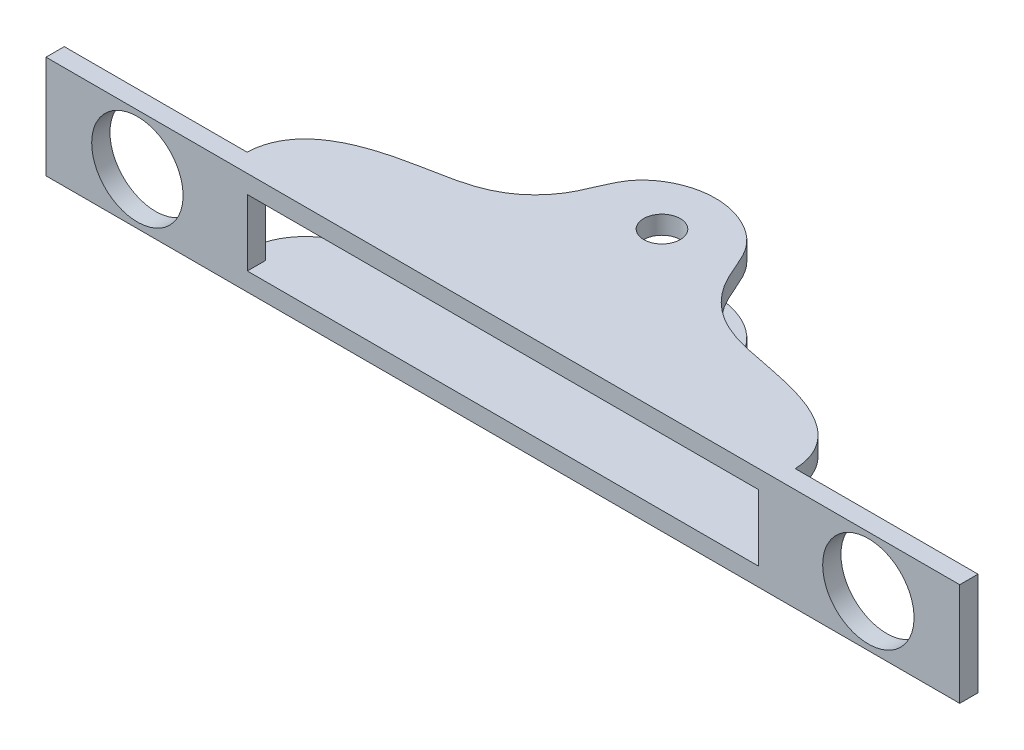
SolidWorks part; units mm, degrees
material "6061 Alloy"
ref_plane "Front Plane" through (0, 0, 0) normal (0, 0, 1) x (1, 0, 0)
ref_plane "Top Plane" through (0, 0, 0) normal (0, 1, 0) x (1, 0, 0)
ref_plane "Right Plane" through (0, 0, 0) normal (1, 0, 0) x (0, 0, -1)
sketch "Sketch2" plane through (0, 0, 0) normal (0, 1, 0) x (1, 0, 0)
  line L0 (0, 0) -> (25.4, 0) construction
  line L1 (0, 0) -> (-25.4, 0) construction
  line L2 (0, 24.8691) -> (0, -5.2934) construction
  line L3 (0, -5.2934) -> (0, 0) construction
  line L4 (0, 9.7878) -> (0, 24.8691) construction
  line L5 (-25.4, 0) -> (-31.75, 0)
  line L6 (25.4, 0) -> (31.75, 0)
  line L7 (-25.4, 0) -> (-19.05, 0)
  line L8 (19.05, 0) -> (25.4, 0)
  line L9 (-31.75, 0) -> (-31.75, -1.27)
  line L10 (-31.75, -1.27) -> (31.75, -1.27)
  line L11 (31.75, -1.27) -> (31.75, 0)
  line L12 (-19.05, 0) -> (19.05, 0)
  circle A0 centre (0, 9.7878) radius 1.27
  spline S0 degree 3 poles (19.05, 0) (18.925, 3.1125) (13.8714, 5.1827) (8.1004, 5.6407) (5.1505, 8.7108) (4.2338, 12.3346) (1.4648, 13.5252) (0, 13.4975) knots 0 0 0 0 0.332449 0.564616 0.691987 0.817132 1 1 1 1
  spline S1 degree 3 poles (-19.05, 0) (-18.925, 3.1125) (-13.8714, 5.1827) (-8.1004, 5.6407) (-5.1505, 8.7108) (-4.2338, 12.3346) (-1.4648, 13.5252) (0, 13.4975) knots 0 0 0 0 0.332449 0.564616 0.691987 0.817132 1 1 1 1
extrude "Boss-Extrude1" add sketch "Sketch2" along normal mid plane 7.1437 contours S1 L12 S0 | L12 L7 L5 L9 L10 L11 L6 L8 region at (0, 0, 0.635) region at (0, 0, -4.3541)
extrude "Cut-Extrude1" cut sketch "Sketch2<3>" against normal mid plane 4.6037 contours S1 L12 S0 region at (0, 0, -4.3541)
sketch "Sketch2<3>" plane through (0, 0, 0) normal (0, 1, 0) x (1, 0, 0) same geometry as "Sketch2"
sketch "Sketch3" plane through (0, 0, 0) normal (0, 0, -1) x (-1, 0, 0)
  line L0 (0, 0) -> (25.4, 0) construction
  line L1 (0, 0) -> (-25.4, 0) construction
  line L2 (-17.7571, 2.3019) -> (-17.7571, -2.3019)
  line L3 (-17.7571, -2.3019) -> (17.7571, -2.3019)
  line L4 (0, -2.3019) -> (0, 2.3019) construction
  line L5 (17.7571, 2.3019) -> (-17.7571, 2.3019)
  line L6 (17.7571, 2.3019) -> (17.7571, -2.3019)
  circle A0 centre (-25.4, 0) radius 3.175
  circle A1 centre (25.4, 0) radius 3.175
extrude "Cut-Extrude2" cut sketch "Sketch3" against normal blind 4.6037
